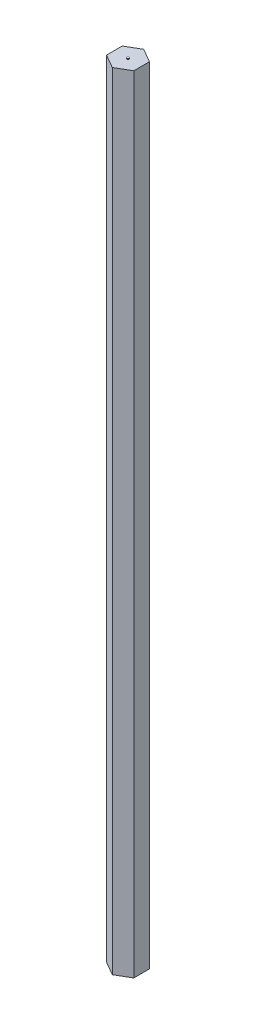
SolidWorks part; units mm, degrees
ref_plane "Front Plane" through (0, 0, 0) normal (0, 0, 1) x (1, 0, 0)
ref_plane "Top Plane" through (0, 0, 0) normal (0, 1, 0) x (1, 0, 0)
ref_plane "Right Plane" through (0, 0, 0) normal (1, 0, 0) x (0, 0, -1)
sketch "Sketch1" plane through (0, 0, 0) normal (0, 1, 0) x (1, 0, 0)
  line L1 (1732.0508, 1000) -> (0, 2000)
  line L2 (0, 2000) -> (-1732.0508, 1000)
  line L3 (-1732.0508, 1000) -> (-1732.0508, -1000)
  line L4 (-1732.0508, -1000) -> (0, -2000)
  line L5 (0, -2000) -> (1732.0508, -1000)
  line L6 (1732.0508, -1000) -> (1732.0508, 1000)
  circle A0 centre (0, 0) radius 2000
  circle A1 centre (0, 0) radius 1732.0508 construction
extrude "Boss-Extrude1" add sketch "Sketch1" along normal blind 100000 contours L5 L6 L1 L2 L3 L4 region at (0, 0, 0)
sketch "Sketch2" plane through (0, 100000, 0) normal (0, 1, 0) x (1, 0, 0)
  circle A0 centre (0, 0) radius 150
  dimension "D1" = 300
extrude "Boss-Extrude2" add sketch "Sketch2" along normal blind 100
